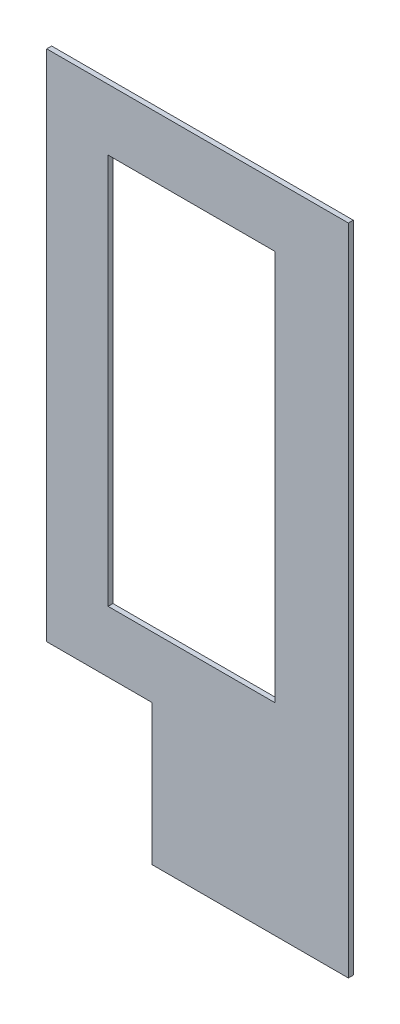
SolidWorks part; units mm, degrees
ref_plane "Спереди" through (0, 0, 0) normal (0, 0, 1) x (1, 0, 0)
ref_plane "Сверху" through (0, 0, 0) normal (0, 1, 0) x (1, 0, 0)
ref_plane "Справа" through (0, 0, 0) normal (1, 0, 0) x (0, 0, -1)
sketch "Эскиз1" plane through (0, 0, 0) normal (0, 1, 0) x (1, 0, 0)
  line L1 (0, 0) -> (245.9852, 0)
  line L2 (0, 0) -> (0, -4)
  line L3 (0, -4) -> (245.9852, -4)
  line L4 (245.9852, 0) -> (245.9852, -4)
extrude "Вытянуть1" add sketch "Эскиз1" along normal up to surface (418.7137 mm away)
sketch "Эскиз2" plane through (0, 0, 0) normal (0, -1, 0) x (1, 0, 0)
  line L0 (245.9852, 0) -> (0, 0) construction
  line L1 (245.9852, 4) -> (85.9852, 4)
  line L2 (245.9852, 4) -> (245.9852, 0)
  line L3 (245.9852, 0) -> (85.9852, 0)
  line L4 (85.9852, 4) -> (85.9852, 0)
extrude "Вытянуть2" add sketch "Эскиз2" along normal up to surface (114.5 mm away)
sketch "Sketch1" plane through (0, 0, 4) normal (0, 0, 1) x (1, 0, 0)
  line L0 (0, 418.7137) -> (245.9852, 418.7137) construction
  line L1 (50, 368.7137) -> (185.9852, 368.7137)
  line L2 (50, 368.7137) -> (50, 50)
  line L3 (50, 50) -> (185.9852, 50)
  line L4 (185.9852, 368.7137) -> (185.9852, 50)
  line L5 (245.9852, 418.7137) -> (245.9852, -114.5) construction
  line L6 (0, 418.7137) -> (0, 0) construction
  line L7 (0, 0) -> (85.9852, 0) construction
  dimension "D1" = 50
  dimension "D2" = 60
  dimension "D3" = 50
  dimension "D4" = 50
extrude "Cut-Extrude1" cut sketch "Sketch1" against normal through all
